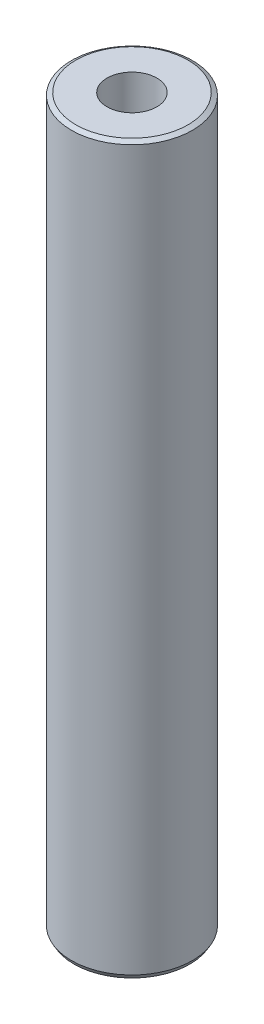
SolidWorks part; units mm, degrees
ref_plane "Front Plane" through (0, 0, 0) normal (0, 0, 1) x (1, 0, 0)
ref_plane "Top Plane" through (0, 0, 0) normal (0, 1, 0) x (1, 0, 0)
ref_plane "Right Plane" through (0, 0, 0) normal (1, 0, 0) x (0, 0, -1)
sketch "Sketch1" plane through (0, 0, 0) normal (0, 1, 0) x (1, 0, 0)
  circle A0 centre (0, 0) radius 50
  dimension "SHAFT_OD" = 100
extrude "Boss-Extrude1" add sketch "Sketch1" along normal blind 600
sketch "Sketch2" plane through (0, 0, 0) normal (0, 1, 0) x (1, 0, 0)
  circle A0 centre (0, 0) radius 20.6194
  dimension "BORE_D" = 41.2388
extrude "Cut-Extrude1" cut sketch "Sketch2" along normal through all
chamfer "Chamfer1" distance 2.1056 angle 60 2 edges at (0, 600, 50) (0, 0, 50) first distance on face at (0, 600, 50) first distance on face at (0, 0, 20.6194)
